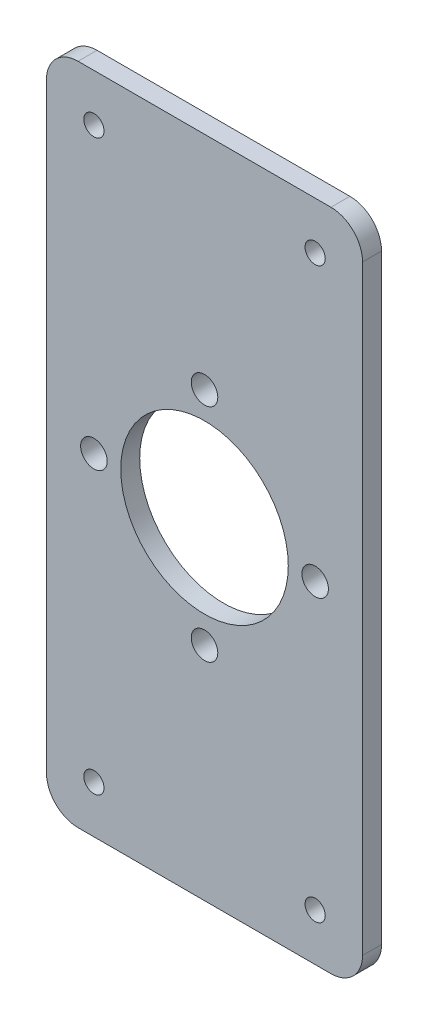
SolidWorks part; units mm, degrees
ref_plane "正面" through (0, 0, 0) normal (0, 0, 1) x (1, 0, 0)
ref_plane "平面" through (0, 0, 0) normal (0, 1, 0) x (1, 0, 0)
ref_plane "右側面" through (0, 0, 0) normal (1, 0, 0) x (0, 0, -1)
sketch "ｽｹｯﾁ2" plane through (0, 0, 0) normal (0, 0, 1) x (1, 0, 0)
  line L0 (25, 105) -> (25, 0) construction
  line L1 (0, 0) -> (50, 0)
  line L2 (0, 0) -> (0, 105)
  line L3 (0, 105) -> (50, 105)
  line L4 (50, 0) -> (50, 105)
  line L5 (7.5, 97.5) -> (42.5, 97.5) construction
  line L6 (7.5, 7.5) -> (42.5, 7.5) construction
  circle A0 centre (25, 52.5) radius 13.25
  circle A1 centre (25, 52.5) radius 17.5 construction
  circle A2 centre (25, 70) radius 2.1
  circle A3 centre (42.5, 52.5) radius 2.1
  circle A4 centre (7.5, 52.5) radius 2.1
  circle A5 centre (25, 35) radius 2.1
  circle A6 centre (7.5, 97.5) radius 1.6
  circle A7 centre (42.5, 97.5) radius 1.6
  circle A8 centre (42.5, 7.5) radius 1.6
  circle A9 centre (7.5, 7.5) radius 1.6
  point P21 (25, 97.5)
  point P24 (25, 7.5)
  dimension "D2" = 26.5
  dimension "D3" = 35
  dimension "D4" = 4.2
  dimension "D6" = 7.5
  dimension "D8" = 7.5
  dimension "D9" = 3.2
  dimension "D1" = 90
  dimension "D5" = 50
  dimension "D7" = 7.5
extrude "ﾎﾞｽ - 押し出し1" add sketch "ｽｹｯﾁ2" along normal blind 3
fillet "ﾌｨﾚｯﾄ1" radius 5 4 edges at (0, 0, 1.5) (50, 0, 1.5) (0, 105, 1.5) (50, 105, 1.5)
